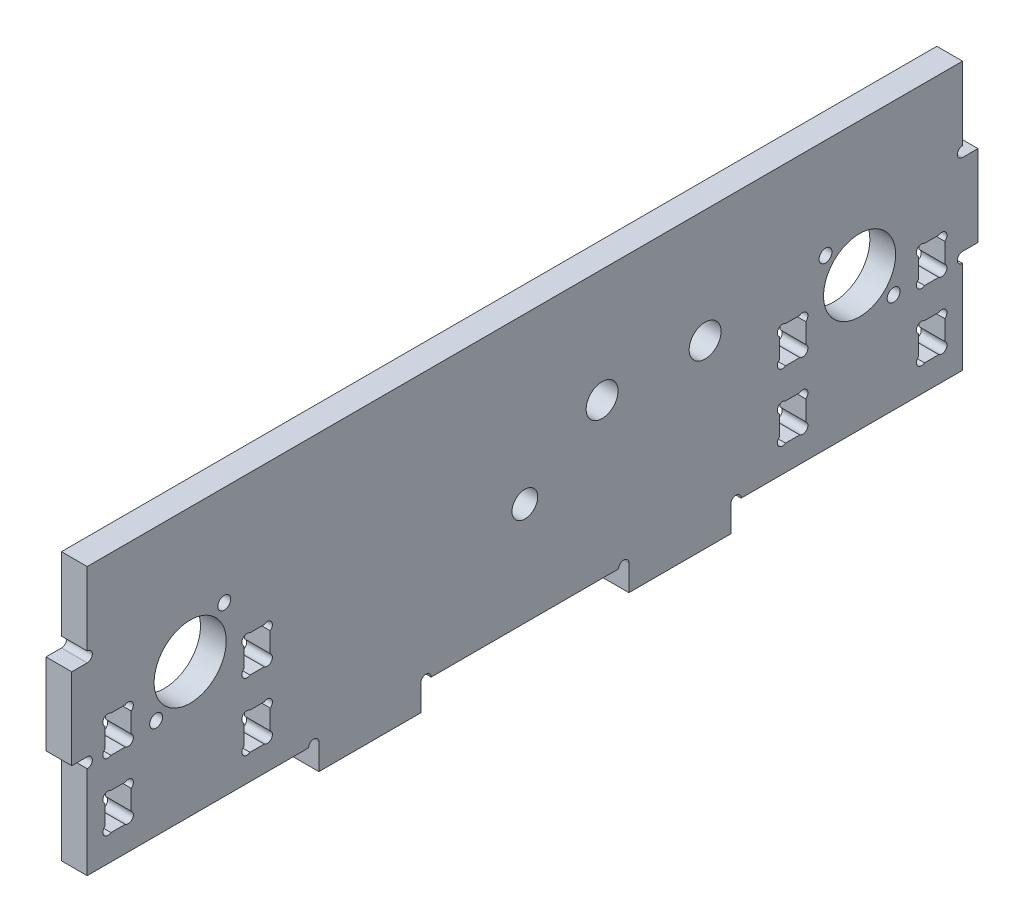
SolidWorks part; units mm, degrees
ref_plane "정면" through (0, 0, 0) normal (0, 0, 1) x (1, 0, 0)
ref_plane "윗면" through (0, 0, 0) normal (0, 1, 0) x (1, 0, 0)
ref_plane "우측면" through (0, 0, 0) normal (1, 0, 0) x (0, 0, -1)
sketch "스케치1" plane through (0, 0, 0) normal (1, 0, 0) x (0, 0, -1)
  line L1 (0, 0) -> (170, 0)
  line L2 (0, 0) -> (0, 52)
  line L3 (0, 52) -> (170, 52)
  line L4 (170, 0) -> (170, 52)
  dimension "D1" = 170
  dimension "D2" = 52
extrude "보스-돌출1" add sketch "스케치1" along normal blind 5
sketch "스케치2" plane through (5, 0, 0) normal (1, 0, 0) x (0, 0, -1)
  line L0 (170, 26) -> (150, 26) construction
  line L1 (170, 0) -> (170, 52) construction
  line L2 (150, 26) -> (20, 26) construction
  line L3 (20, 26) -> (0, 26) construction
  line L4 (0, 52) -> (0, 0) construction
  circle A0 centre (150, 26) radius 7
  circle A1 centre (20, 26) radius 7
  dimension "D2" = 14
  dimension "D1" = 20
extrude "컷-돌출1" cut sketch "스케치2" against normal blind 10
sketch "스케치3" plane through (5, 0, 0) normal (1, 0, 0) x (0, 0, -1)
  line L0 (0, 0) -> (170, 0) construction
  line L1 (45, 0) -> (64.8, 0)
  line L2 (45, 0) -> (45, -5)
  line L3 (45, -5) -> (64.8, -5)
  line L4 (64.8, 0) -> (64.8, -5)
  line L5 (0, -5) -> (44.9, -5) construction
  line L6 (64.8, -5) -> (105.2, -5) construction
  line L7 (125, 0) -> (105.2, 0)
  line L8 (125, 0) -> (125, -5)
  line L9 (125, -5) -> (105.2, -5)
  line L10 (105.2, 0) -> (105.2, -5)
  line L11 (125, -5) -> (170, -5) construction
  line L12 (170, -5) -> (170, 0) construction
  line L13 (0, 0) -> (0, -5) construction
  line L14 (0, 0) -> (0, -5) construction
  line L15 (0, -5) -> (45, -5) construction
  dimension "D1" = 45
  dimension "D2" = 19.8
extrude "보스-돌출2" add sketch "스케치3" against normal blind 5
sketch "스케치6" plane through (5, 0, 0) normal (1, 0, 0) x (0, 0, -1)
  line L0 (151.2, 0) -> (151.2, 6)
  line L1 (148.1, 10) -> (151.2, 10) construction
  line L2 (146.9, 6) -> (146.9, 8.8) construction
  line L3 (151.2, 6) -> (151.2, 8.8) construction
  line L4 (148.1, 0) -> (151.2, 0)
  line L5 (146.9, 8.8) -> (148.1, 8.8)
  line L6 (148.1, 0) -> (148.1, 6)
  line L7 (152.4, 8.8) -> (152.4, 6) construction
  line L8 (148.1, 6) -> (146.9, 6)
  line L9 (148.1, 8.8) -> (148.1, 6) construction
  line L10 (151.2, 8.8) -> (151.2, 10)
  line L11 (148.1, 6) -> (151.2, 6) construction
  line L12 (148.1, 8.8) -> (151.2, 8.8) construction
  line L13 (151.2, 8.8) -> (152.4, 8.8)
  line L14 (148.1, 8.8) -> (148.1, 10)
  line L15 (149.65, 10) -> (149.65, 12.1831) construction
  line L16 (152.4, 6) -> (151.2, 6)
  line L18 (64.8, 0) -> (105.2, 0) construction
  line L19 (101.2, 0) -> (101.2, 6)
  line L20 (98.1, 10) -> (101.2, 10) construction
  line L21 (96.9, 6) -> (96.9, 8.8) construction
  line L22 (101.2, 6) -> (101.2, 8.8) construction
  line L23 (98.1, 0) -> (101.2, 0)
  line L24 (96.9, 8.8) -> (98.1, 8.8)
  line L25 (98.1, 0) -> (98.1, 6)
  line L26 (102.4, 8.8) -> (102.4, 6) construction
  line L27 (98.1, 6) -> (96.9, 6)
  line L28 (98.1, 8.8) -> (98.1, 6) construction
  line L29 (101.2, 8.8) -> (101.2, 10)
  line L30 (98.1, 6) -> (101.2, 6) construction
  line L31 (98.1, 8.8) -> (101.2, 8.8) construction
  line L32 (101.2, 8.8) -> (102.4, 8.8)
  line L33 (98.1, 8.8) -> (98.1, 10)
  line L34 (99.65, 10) -> (99.65, 12.1831) construction
  line L35 (102.4, 6) -> (101.2, 6)
  line L37 (105.2, 0) -> (105.2, -5) construction
  line L71 (85, 52) -> (85, 0) construction
  line L72 (170, 52) -> (0, 52) construction
  line L89 (70.35, 10) -> (70.35, 12.1831) construction
  line L90 (71.9, 8.8) -> (68.8, 8.8) construction
  line L91 (71.9, 6) -> (68.8, 6) construction
  line L92 (71.9, 8.8) -> (71.9, 6) construction
  line L93 (67.6, 8.8) -> (67.6, 6) construction
  line L94 (68.8, 6) -> (68.8, 8.8) construction
  line L95 (73.1, 6) -> (73.1, 8.8) construction
  line L96 (71.9, 10) -> (68.8, 10) construction
  line L97 (20.35, 10) -> (20.35, 12.1831) construction
  line L98 (21.9, 8.8) -> (18.8, 8.8) construction
  line L99 (21.9, 6) -> (18.8, 6) construction
  line L100 (21.9, 8.8) -> (21.9, 6) construction
  line L101 (17.6, 8.8) -> (17.6, 6) construction
  line L102 (18.8, 6) -> (18.8, 8.8) construction
  line L103 (23.1, 6) -> (23.1, 8.8) construction
  line L104 (21.9, 10) -> (18.8, 10) construction
  line L123 (67.6, 6) -> (68.8, 6)
  line L124 (71.9, 8.8) -> (71.9, 10)
  line L125 (68.8, 8.8) -> (67.6, 8.8)
  line L126 (68.8, 8.8) -> (68.8, 10)
  line L127 (71.9, 6) -> (73.1, 6)
  line L128 (71.9, 0) -> (71.9, 6)
  line L129 (73.1, 8.8) -> (71.9, 8.8)
  line L130 (71.9, 0) -> (68.8, 0)
  line L131 (68.8, 0) -> (68.8, 6)
  line L132 (17.6, 6) -> (18.8, 6)
  line L133 (21.9, 8.8) -> (21.9, 10)
  line L134 (18.8, 8.8) -> (17.6, 8.8)
  line L135 (18.8, 8.8) -> (18.8, 10)
  line L136 (21.9, 6) -> (23.1, 6)
  line L137 (21.9, 0) -> (21.9, 6)
  line L138 (23.1, 8.8) -> (21.9, 8.8)
  line L139 (21.9, 0) -> (18.8, 0)
  line L140 (18.8, 0) -> (18.8, 6)
  arc A0 (151.2, 10) -> (148.1, 10) centre (149.65, 10) ccw
  arc A1 (146.9, 8.8) -> (146.9, 6) centre (146.9, 7.4) ccw
  arc A2 (152.4, 6) -> (152.4, 8.8) centre (152.4, 7.4) ccw
  arc A3 (101.2, 10) -> (98.1, 10) centre (99.65, 10) ccw
  arc A4 (96.9, 8.8) -> (96.9, 6) centre (96.9, 7.4) ccw
  arc A5 (102.4, 6) -> (102.4, 8.8) centre (102.4, 7.4) ccw
  arc A18 (67.6, 6) -> (67.6, 8.8) centre (67.6, 7.4) cw
  arc A19 (73.1, 8.8) -> (73.1, 6) centre (73.1, 7.4) cw
  arc A20 (68.8, 10) -> (71.9, 10) centre (70.35, 10) cw
  arc A21 (17.6, 6) -> (17.6, 8.8) centre (17.6, 7.4) cw
  arc A22 (23.1, 8.8) -> (23.1, 6) centre (23.1, 7.4) cw
  arc A23 (18.8, 10) -> (21.9, 10) centre (20.35, 10) cw
  dimension "D1" = 3.1
  dimension "D2" = 4
  dimension "D3" = 5.5
  dimension "D4" = 2.8
  dimension "D7" = 3.1
  dimension "D9" = 5.5
  dimension "D10" = 2.8
  dimension "D12" = 50
extrude "컷-돌출2" [suppressed] cut sketch "스케치6" against normal blind 10
sketch "스케치8" plane through (5, 0, 0) normal (1, 0, 0) x (0, 0, -1)
  line L0 (170, 0) -> (170, 52) construction
  line L1 (170, 35.8) -> (173, 35.8)
  line L2 (170, 35.8) -> (170, 20)
  line L3 (170, 20) -> (173, 20)
  line L4 (173, 35.8) -> (173, 20)
  line L5 (173, 52) -> (173, 35.9) construction
  line L8 (85, 0) -> (85, 52) construction
  line L10 (170, 52) -> (0, 52) construction
  line L11 (-3, 35.8) -> (-3, 20)
  line L12 (0, 20) -> (-3, 20)
  line L13 (0, 35.8) -> (0, 20)
  line L14 (0, 35.8) -> (-3, 35.8)
  line L15 (125, 0) -> (170, 0) construction
  dimension "D1" = 20
  dimension "D2" = 15.8
extrude "보스-돌출3" add sketch "스케치8" against normal blind 5
sketch "스케치7" plane through (5, 0, 0) normal (1, 0, 0) x (0, 0, -1)
  line L0 (64.8, 0) -> (105.2, 0) construction
  line L1 (0, 0) -> (45, 0) construction
  line L2 (64.8, 0) -> (105.2, 0) construction
  line L3 (125, 0) -> (170, 0) construction
  line L4 (170, 35.8) -> (170, 52) construction
  line L5 (170, 0) -> (170, 20) construction
  line L6 (0, 52) -> (0, 35.8) construction
  line L7 (0, 20) -> (0, 0) construction
  circle A0 centre (65.8, 0) radius 1
  circle A1 centre (44, 0) radius 1
  circle A2 centre (104.2, 0) radius 1
  circle A3 centre (126, 0) radius 1
  circle A4 centre (170, 36.8) radius 1
  circle A5 centre (170, 19) radius 1
  circle A6 centre (0, 36.8) radius 1
  circle A7 centre (0, 19) radius 1
  dimension "D1" = 2
extrude "컷-돌출3" cut sketch "스케치7" against normal blind 10
sketch "스케치10" plane through (0, 0, 0) normal (-1, 0, 0) x (0, 0, 1)
  line L0 (-166.55, 25.05) -> (-161.45, 17.95) construction
  line L1 (-166.55, 17.95) -> (-161.45, 17.95)
  line L2 (-166.55, 17.95) -> (-166.55, 25.05)
  line L3 (-166.55, 25.05) -> (-161.45, 25.05)
  line L4 (-161.45, 17.95) -> (-161.45, 25.05)
  line L5 (-161.45, 25.05) -> (-166.55, 17.95) construction
  line L6 (-85, 52) -> (-85, 0) construction
  line L7 (-139.55, 17.95) -> (-134.45, 17.95)
  line L8 (-139.55, 17.95) -> (-139.55, 25.05)
  line L9 (-139.55, 25.05) -> (-134.45, 25.05)
  line L10 (-134.45, 17.95) -> (-134.45, 25.05)
  line L11 (-166.55, 4.95) -> (-161.45, 4.95)
  line L12 (-166.55, 4.95) -> (-166.55, 12.05)
  line L13 (-166.55, 12.05) -> (-161.45, 12.05)
  line L14 (-161.45, 4.95) -> (-161.45, 12.05)
  line L15 (-139.55, 12.05) -> (-134.45, 12.05)
  line L16 (-139.55, 12.05) -> (-139.55, 4.95)
  line L17 (-139.55, 4.95) -> (-134.45, 4.95)
  line L18 (-134.45, 12.05) -> (-134.45, 4.95)
  line L19 (-170, 52) -> (0, 52) construction
  line L20 (-139.5, 5) -> (-139.5, 40) construction
  line L21 (-8.55, 25.05) -> (-3.45, 17.95) construction
  line L22 (-3.45, 25.05) -> (-8.55, 17.95) construction
  line L23 (-35.55, 12.05) -> (-35.55, 4.95)
  line L24 (-30.45, 4.95) -> (-35.55, 4.95)
  line L25 (-30.45, 12.05) -> (-30.45, 4.95)
  line L26 (-30.45, 12.05) -> (-35.55, 12.05)
  line L27 (-8.55, 4.95) -> (-8.55, 12.05)
  line L28 (-3.45, 12.05) -> (-8.55, 12.05)
  line L29 (-3.45, 4.95) -> (-3.45, 12.05)
  line L30 (-3.45, 4.95) -> (-8.55, 4.95)
  line L31 (-35.55, 17.95) -> (-35.55, 25.05)
  line L32 (-30.45, 25.05) -> (-35.55, 25.05)
  line L33 (-30.45, 17.95) -> (-30.45, 25.05)
  line L34 (-30.45, 17.95) -> (-35.55, 17.95)
  line L35 (-8.55, 17.95) -> (-8.55, 25.05)
  line L36 (-3.45, 25.05) -> (-8.55, 25.05)
  line L37 (-3.45, 17.95) -> (-3.45, 25.05)
  line L38 (-3.45, 17.95) -> (-8.55, 17.95)
  line L39 (-134.5, 5) -> (-134.5, 40) construction
  line L40 (-134.5, 25) -> (-139.5, 25) construction
  line L41 (-134.5, 18) -> (-139.5, 18) construction
  line L42 (-161.5, 12) -> (-166.5, 12) construction
  line L43 (-166.5, 5) -> (-161.5, 5) construction
  line L44 (-161.5, 5) -> (-161.5, 40) construction
  line L45 (-166.5, 5) -> (-166.5, 40) construction
  dimension "D1" = 0.05
  dimension "D2" = 0.05
  dimension "D3" = 0.05
  dimension "D4" = 0.05
  dimension "D5" = 0.05
  dimension "D6" = 0.05
  dimension "D7" = 0.05
  dimension "D8" = 0.05
extrude "컷-돌출4" cut sketch "스케치10" against normal blind 10
sketch "스케치11" plane through (5, 0, 0) normal (1, 0, 0) x (0, 0, -1)
  line L0 (85, 52) -> (85, 0) construction
  line L1 (170, 52) -> (0, 52) construction
  line L3 (161.45, 25.05) -> (166.55, 17.95) construction
  line L4 (166.55, 25.05) -> (161.45, 17.95) construction
  line L5 (139.55, 17.95) -> (161.45, 17.95) construction
  line L6 (161.45, 17.95) -> (161.45, 12.05) construction
  line L7 (161.45, 12.05) -> (139.55, 12.05) construction
  line L8 (139.55, 12.05) -> (139.55, 17.95) construction
  line L9 (150.5, 17.95) -> (150.5, 12.05) construction
  line L10 (139.55, 15) -> (161.45, 15) construction
  line L11 (134.45, 25.05) -> (139.55, 17.95) construction
  line L12 (139.55, 25.05) -> (134.45, 17.95) construction
  line L13 (139.55, 4.95) -> (134.45, 12.05) construction
  line L14 (134.45, 4.95) -> (139.55, 12.05) construction
  line L15 (166.55, 4.95) -> (161.45, 12.05) construction
  line L16 (161.45, 4.95) -> (166.55, 12.05) construction
  line L17 (8.55, 4.95) -> (3.45, 12.05) construction
  line L18 (3.45, 4.95) -> (8.55, 12.05) construction
  line L19 (35.55, 4.95) -> (30.45, 12.05) construction
  line L20 (30.45, 4.95) -> (35.55, 12.05) construction
  line L21 (30.45, 25.05) -> (35.55, 17.95) construction
  line L22 (35.55, 25.05) -> (30.45, 17.95) construction
  line L23 (30.45, 15) -> (8.55, 15) construction
  line L24 (19.5, 17.95) -> (19.5, 12.05) construction
  line L25 (30.45, 12.05) -> (30.45, 17.95) construction
  line L26 (8.55, 12.05) -> (30.45, 12.05) construction
  line L27 (8.55, 17.95) -> (8.55, 12.05) construction
  line L28 (30.45, 17.95) -> (8.55, 17.95) construction
  line L29 (3.45, 25.05) -> (8.55, 17.95) construction
  line L30 (8.55, 25.05) -> (3.45, 17.95) construction
  circle A0 centre (165.9666, 24.2378) radius 1
  circle A1 centre (162.0334, 24.2378) radius 1
  circle A2 centre (165.9666, 18.7622) radius 1
  circle A3 centre (162.0334, 18.7622) radius 1
  circle A4 centre (138.9666, 18.7622) radius 1
  circle A5 centre (135.0334, 18.7622) radius 1
  circle A6 centre (138.9666, 24.2378) radius 1
  circle A7 centre (135.0334, 24.2378) radius 1
  circle A8 centre (135.0334, 5.7622) radius 1
  circle A9 centre (138.9666, 5.7622) radius 1
  circle A10 centre (135.0334, 11.2378) radius 1
  circle A11 centre (138.9666, 11.2378) radius 1
  circle A12 centre (162.0334, 11.2378) radius 1
  circle A13 centre (165.9666, 11.2378) radius 1
  circle A14 centre (162.0334, 5.7622) radius 1
  circle A15 centre (165.9666, 5.7622) radius 1
  circle A16 centre (4.0334, 5.7622) radius 1
  circle A17 centre (7.9666, 5.7622) radius 1
  circle A18 centre (4.0334, 11.2378) radius 1
  circle A19 centre (7.9666, 11.2378) radius 1
  circle A20 centre (31.0334, 11.2378) radius 1
  circle A21 centre (34.9666, 11.2378) radius 1
  circle A22 centre (31.0334, 5.7622) radius 1
  circle A23 centre (34.9666, 5.7622) radius 1
  circle A24 centre (34.9666, 24.2378) radius 1
  circle A25 centre (31.0334, 24.2378) radius 1
  circle A26 centre (34.9666, 18.7622) radius 1
  circle A27 centre (31.0334, 18.7622) radius 1
  circle A28 centre (7.9666, 18.7622) radius 1
  circle A29 centre (4.0334, 18.7622) radius 1
  circle A30 centre (7.9666, 24.2378) radius 1
  circle A31 centre (4.0334, 24.2378) radius 1
  dimension "D1" = 2
extrude "컷-돌출5" cut sketch "스케치11" against normal blind 10
sketch "스케치12" plane through (5, 0, 0) normal (1, 0, 0) x (0, 0, -1)
  line L0 (170, 42) -> (162, 42)
  line L1 (158, 38.9) -> (158, 42) construction
  line L2 (162, 37.7) -> (159.2, 37.7) construction
  line L3 (162, 42) -> (159.2, 42) construction
  line L4 (170, 38.9) -> (170, 42)
  line L5 (159.2, 37.7) -> (159.2, 38.9)
  line L6 (170, 38.9) -> (162, 38.9)
  line L7 (159.2, 43.2) -> (162, 43.2) construction
  line L8 (162, 38.9) -> (162, 37.7)
  line L9 (159.2, 38.9) -> (162, 38.9) construction
  line L10 (159.2, 42) -> (158, 42)
  line L11 (162, 38.9) -> (162, 42) construction
  line L12 (159.2, 38.9) -> (159.2, 42) construction
  line L13 (159.2, 42) -> (159.2, 43.2)
  line L14 (159.2, 38.9) -> (158, 38.9)
  line L15 (158, 40.45) -> (156.45, 40.45) construction
  line L16 (162, 43.2) -> (162, 42)
  line L17 (160.6, 37.7) -> (160.6, 38.9) construction
  line L18 (160.6, 43.2) -> (160.6, 42) construction
  line L19 (159.2, 40.45) -> (158, 40.45) construction
  line L20 (160.6, 43.2) -> (160.6, 44.6) construction
  line L21 (160.6, 37.7) -> (160.6, 36.3) construction
  line L22 (170, 37.8) -> (170, 52) construction
  line L23 (170, 52) -> (0, 52) construction
  line L24 (85, 52) -> (85, 0) construction
  line L26 (9.4, 37.7) -> (9.4, 36.3) construction
  line L27 (9.4, 43.2) -> (9.4, 44.6) construction
  line L28 (10.8, 40.45) -> (12, 40.45) construction
  line L29 (9.4, 43.2) -> (9.4, 42) construction
  line L30 (9.4, 37.7) -> (9.4, 38.9) construction
  line L31 (12, 40.45) -> (13.55, 40.45) construction
  line L32 (10.8, 38.9) -> (10.8, 42) construction
  line L33 (8, 38.9) -> (8, 42) construction
  line L34 (10.8, 38.9) -> (8, 38.9) construction
  line L35 (10.8, 43.2) -> (8, 43.2) construction
  line L36 (8, 42) -> (10.8, 42) construction
  line L37 (8, 37.7) -> (10.8, 37.7) construction
  line L38 (12, 38.9) -> (12, 42) construction
  line L39 (8, 43.2) -> (8, 42)
  line L40 (10.8, 38.9) -> (12, 38.9)
  line L41 (10.8, 42) -> (10.8, 43.2)
  line L42 (10.8, 42) -> (12, 42)
  line L43 (8, 38.9) -> (8, 37.7)
  line L44 (0, 38.9) -> (8, 38.9)
  line L45 (10.8, 37.7) -> (10.8, 38.9)
  line L46 (0, 38.9) -> (0, 42)
  line L47 (0, 42) -> (8, 42)
  arc A0 (158, 42) -> (158, 38.9) centre (158, 40.45) ccw
  arc A1 (159.2, 37.7) -> (162, 37.7) centre (160.6, 37.7) ccw
  arc A2 (162, 43.2) -> (159.2, 43.2) centre (160.6, 43.2) ccw
  arc A3 (8, 43.2) -> (10.8, 43.2) centre (9.4, 43.2) cw
  arc A4 (10.8, 37.7) -> (8, 37.7) centre (9.4, 37.7) cw
  arc A5 (12, 42) -> (12, 38.9) centre (12, 40.45) cw
  dimension "D1" = 3.1
  dimension "D2" = 5.5
  dimension "D3" = 2.8
  dimension "D4" = 1.2
  dimension "D5" = 10
  dimension "D6" = 3.1
  dimension "D7" = 8
extrude "컷-돌출6" [suppressed] cut sketch "스케치12" against normal blind 10
sketch "스케치13" plane through (5, 0, 0) normal (1, 0, 0) x (0, 0, -1)
  line L0 (120, 30) -> (100, 30) construction
  line L1 (127, 0) -> (170, 0) construction
  line L2 (170, 37.8) -> (170, 52) construction
  line L4 (66.8, 0) -> (103.2, 0) construction
  circle A0 centre (100, 30) radius 3.1
  circle A1 centre (120, 30) radius 3.1
  circle A2 centre (85, 20) radius 2.5
  dimension "D1" = 6.2
  dimension "D5" = 20
  dimension "D6" = 5
  dimension "D2" = 20
  dimension "D3" = 30
  dimension "D4" = 50
extrude "컷-돌출7" cut sketch "스케치13" against normal blind 10
sketch "스케치14" plane through (5, 0, 0) normal (1, 0, 0) x (0, 0, -1)
  line L0 (150, 26) -> (155.6569, 20.3431) construction
  line L1 (155.6569, 20.3431) -> (156.6114, 19.3886) construction
  line L2 (150, 26) -> (150, 14.9084) construction
  line L3 (150, 26) -> (155.6569, 31.6569) construction
  line L4 (85, 52) -> (85, 0) construction
  line L5 (170, 52) -> (0, 52) construction
  circle A1 centre (150, 26) radius 8 construction
  circle A2 centre (156.6114, 19.3886) radius 1.25
  circle A3 centre (143.3886, 32.6114) radius 1.25
  circle A4 centre (13.3886, 19.3886) radius 1.25
  circle A5 centre (26.6114, 32.6114) radius 1.25
  dimension "D1" = 2.5
  dimension "D2" = 1.35
  dimension "D3" = 45
extrude "컷-돌출8" cut sketch "스케치14" against normal blind 10
